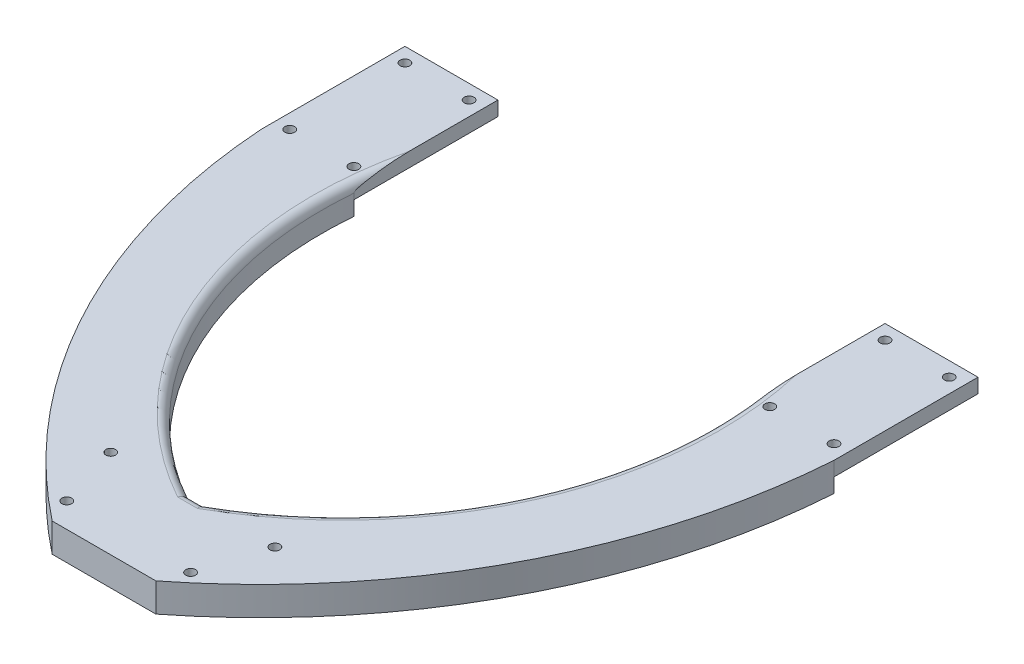
SolidWorks part; units mm, degrees
ref_plane "Ebene vorne" through (0, 0, 0) normal (0, 0, 1) x (1, 0, 0)
ref_plane "Ebene oben" through (0, 0, 0) normal (0, 1, 0) x (1, 0, 0)
ref_plane "Ebene rechts" through (0, 0, 0) normal (1, 0, 0) x (0, 0, -1)
sketch "Skizze1" plane through (0, 0, 0) normal (0, 1, 0) x (1, 0, 0)
  line L1 (-99.5, -210) -> (99.5, -210)
  line L2 (-99.5, -210) -> (-99.5, 210)
  line L3 (-99.5, 210) -> (99.5, 210)
  line L4 (99.5, -210) -> (99.5, 210)
  line L5 (-99.5, -210) -> (99.5, 210) construction
  line L6 (-99.5, 210) -> (99.5, -210) construction
  point P0 (0, 0)
  dimension "D1" = 199
  dimension "D2" = 420
extrude "Aufsatz-Linear austragen1" add sketch "Skizze1" along normal blind 10
ref_plane "Ebene1" through (0, -97.5366, 81.8429) normal (0, -0.766, 0.6428) x (1, 0, 0)
sketch "Skizze2" plane through (0, -97.5366, 81.8429) normal (0, -0.766, 0.6428) x (1, 0, 0)
  line L1 (-99.5, 167.2972) -> (99.5, 167.2972) construction
  circle A0 centre (0, 147.2972) radius 5
  dimension "D1" = 10
  dimension "D2" = 20
extrude "Schnitt-Linear austragen1" [suppressed] cut sketch "Skizze2" against normal blind 30 and the other way blind 10
sketch "Skizze3" [suppressed] plane through (0, -67.9923, 57.0523) normal (0, -0.766, 0.6428) x (1, 0, 0)
  circle A0 centre (0, 101.3345) radius 5
  dimension "D1" = 10
extrude "Aufsatz-Linear austragen2" [suppressed] add sketch "Skizze3" along normal blind 0.1
sketch "Skizze4" plane through (0, -97.5366, 81.8429) normal (0, -0.766, 0.6428) x (1, 0, 0)
  line L0 (0, 167.2972) -> (0, 159.9002) construction
  line L1 (-99.5, 167.2972) -> (99.5, 167.2972) construction
  line L2 (-25, 167.2972) -> (-25, 202.2972)
  line L3 (-25, 202.2972) -> (25, 202.2972)
  line L4 (-25, 167.2972) -> (25, 167.2972)
  line L5 (25, 167.2972) -> (25, 202.2972)
  point P10 (0, 202.2972)
  dimension "D1" = 50
  dimension "D2" = 35
extrude "Aufsatz-Linear austragen3" [suppressed] add sketch "Skizze4" against normal blind 10 separate body
sketch "Skizze5" plane through (0, 10, 0) normal (0, 1, 0) x (1, 0, 0)
  line L0 (0, 0) -> (0, -210) construction
  line L1 (-99.5, -210) -> (99.5, -210) construction
  line L2 (99.5, -210) -> (18, -210)
  line L3 (-18, -210) -> (-99.5, -56)
  line L4 (-99.5, 210) -> (-99.5, -210) construction
  line L5 (-99.5, -56) -> (-99.5, -210)
  line L6 (-99.5, -210) -> (-18, -210)
  line L7 (99.5, -56) -> (99.5, -210)
  line L8 (18, -210) -> (99.5, -56)
  line L9 (-99.5, 210) -> (-99.5, 125)
  line L10 (-99.5, 125) -> (99.5, 125)
  line L11 (99.5, -210) -> (99.5, 210) construction
  line L12 (99.5, 125) -> (99.5, 210)
  line L13 (99.5, 210) -> (-99.5, 210)
  line L14 (67.211, -56) -> (-67.211, -56)
  line L15 (-67.211, -56) -> (-2.6461, -178)
  line L16 (67.211, -56) -> (2.6461, -178)
  line L17 (-2.6461, -178) -> (2.6461, -178)
  line L18 (2.6461, -178) -> (0, -183) construction
  line L19 (-2.6461, -178) -> (0, -183) construction
  point P27 (0, -56)
  dimension "D1" = 36
  dimension "D2" = 154
  dimension "D3" = 85
  dimension "D4" = 32
  dimension "D5" = 27
extrude "Schnitt-Linear austragen2" cut sketch "Skizze5" against normal blind 10
sketch "Skizze6" plane through (0, 10, 0) normal (0, 1, 0) x (1, 0, 0)
  line L0 (0, -210) -> (0, -178) construction
  line L1 (-18, -210) -> (18, -210) construction
  line L2 (-2.6461, -178) -> (2.6461, -178) construction
  line L3 (0, -196.59) -> (-21.075, -196.59) construction
  circle A0 centre (-11, -205) radius 1.7
  circle A1 centre (-11, -188.18) radius 1.7
  circle A2 centre (11, -205) radius 1.7
  circle A3 centre (11, -188.18) radius 1.7
  dimension "D1" = 3.4
  dimension "D2" = 11
  dimension "D3" = 5
  dimension "D4" = 13.41
extrude "Schnitt-Linear austragen3" [suppressed] cut sketch "Skizze6" against normal through all
sketch "Skizze7" [suppressed] plane through (0, 0, 0) normal (0, -1, 0) x (1, 0, 0)
  line L0 (-11, 205) -> (-11, 210) construction
  line L1 (-18, 210) -> (18, 210) construction
  line L2 (-11, 205) -> (-5.1092, 205) construction
  line L3 (-11, 208.4064) -> (-8.05, 206.7032)
  line L4 (-8.05, 206.7032) -> (-8.05, 203.2968)
  line L5 (-11, 201.5936) -> (-8.05, 203.2968)
  line L6 (-11, 201.5936) -> (-13.95, 203.2968)
  line L7 (-13.95, 206.7032) -> (-13.95, 203.2968)
  line L8 (-11, 208.4064) -> (-13.95, 206.7032)
  line L9 (0, 210) -> (0, 121.6034) construction
  line L10 (11, 205) -> (11, 188.18) construction
  line L11 (11, 196.59) -> (0, 196.59) construction
  line L12 (11, 208.4064) -> (8.05, 206.7032)
  line L13 (11, 201.5936) -> (8.05, 203.2968)
  line L14 (8.05, 206.7032) -> (8.05, 203.2968)
  line L15 (11, 201.5936) -> (13.95, 203.2968)
  line L16 (13.95, 206.7032) -> (13.95, 203.2968)
  line L17 (11, 208.4064) -> (13.95, 206.7032)
  line L18 (-8.05, 186.4768) -> (-8.05, 189.8832)
  line L19 (-11, 191.5864) -> (-13.95, 189.8832)
  line L20 (-11, 191.5864) -> (-8.05, 189.8832)
  line L21 (-13.95, 186.4768) -> (-13.95, 189.8832)
  line L22 (-11, 184.7736) -> (-13.95, 186.4768)
  line L23 (-11, 184.7736) -> (-8.05, 186.4768)
  line L24 (8.05, 186.4768) -> (8.05, 189.8832)
  line L25 (11, 191.5864) -> (8.05, 189.8832)
  line L26 (11, 191.5864) -> (13.95, 189.8832)
  line L27 (13.95, 186.4768) -> (13.95, 189.8832)
  line L28 (11, 184.7736) -> (13.95, 186.4768)
  line L29 (11, 184.7736) -> (8.05, 186.4768)
  point P10 (-8.05, 205)
  dimension "D1" = 120
  dimension "D2" = 5.9
extrude "Schnitt-Linear austragen4" [suppressed] cut sketch "Skizze7" against normal blind 4
sketch "Skizze8" plane through (0, 10, 0) normal (0, 1, 0) x (1, 0, 0)
  line L0 (99.5, 115.41) -> (78.872, 115.41) construction
  line L1 (99.5, -56) -> (99.5, 125) construction
  line L2 (-99.5, 125) -> (99.5, 125) construction
  dimension "D1" = 9.59
ref_plane "Ebene2" through (0, 62.6966, -52.6087) normal (0, 0.766, -0.6428) x (-1, 0, 0)
sketch "Skizze9" plane through (0, 62.6966, -52.6087) normal (0, 0.766, -0.6428) x (-1, 0, 0)
  line L0 (-99.5, -81.9813) -> (-78.872, -81.9813) construction
  line L1 (-99.5, 49.3264) -> (-99.5, -89.3277) construction
  line L2 (0, -45.2589) -> (0, -16.2619) construction
  circle A0 centre (-94.5, -81.9813) radius 1.7
  circle A1 centre (94.5, -81.9813) radius 1.7
  circle A2 centre (-30, -81.9813) radius 1.7
  circle A3 centre (30, -81.9813) radius 1.7
  dimension "D1" = 3.4
  dimension "D2" = 5
  dimension "D3" = 30
extrude "Schnitt-Linear austragen5" [suppressed] cut sketch "Skizze9" against normal through all and the other way through all
ref_plane "Ebene3" through (0, 55.0361, -46.1808) normal (0, 0.766, -0.6428) x (-1, 0, 0)
sketch "Skizze10" [suppressed] plane through (0, 55.0361, -46.1808) normal (0, 0.766, -0.6428) x (-1, 0, 0)
  line L0 (-95, -81.9813) -> (-100, -81.9813) construction
  line L1 (-95, -81.9813) -> (-95, -30.0694) construction
  line L2 (-95, -78.7482) -> (-97.8, -80.3647)
  line L3 (-97.8, -80.3647) -> (-97.8, -83.5979)
  line L4 (-95, -85.2145) -> (-97.8, -83.5979)
  line L5 (-95, -85.2145) -> (-92.2, -83.5979)
  line L6 (-92.2, -80.3647) -> (-92.2, -83.5979)
  line L7 (-95, -78.7482) -> (-92.2, -80.3647)
  line L8 (0, 0) -> (0, -45.6283) construction
  line L9 (-30, -81.9813) -> (-95, -81.9813) construction
  line L10 (-62.5, -81.9813) -> (-62.5, -23.1343) construction
  line L11 (-32.8, -80.3647) -> (-32.8, -83.5979)
  line L12 (-30, -85.2145) -> (-32.8, -83.5979)
  line L13 (-30, -85.2145) -> (-27.2, -83.5979)
  line L14 (-27.2, -80.3647) -> (-27.2, -83.5979)
  line L15 (-30, -78.7482) -> (-27.2, -80.3647)
  line L16 (-30, -78.7482) -> (-32.8, -80.3647)
  line L17 (95, -78.7482) -> (92.2, -80.3647)
  line L18 (92.2, -80.3647) -> (92.2, -83.5979)
  line L19 (95, -85.2145) -> (92.2, -83.5979)
  line L20 (95, -85.2145) -> (97.8, -83.5979)
  line L21 (97.8, -80.3647) -> (97.8, -83.5979)
  line L22 (95, -78.7482) -> (97.8, -80.3647)
  line L23 (30, -78.7482) -> (32.8, -80.3647)
  line L24 (30, -78.7482) -> (27.2, -80.3647)
  line L25 (27.2, -80.3647) -> (27.2, -83.5979)
  line L26 (30, -85.2145) -> (27.2, -83.5979)
  line L27 (30, -85.2145) -> (32.8, -83.5979)
  line L28 (32.8, -80.3647) -> (32.8, -83.5979)
  point P9 (-97.8, -81.9813)
  point P31 (97.8, -81.9813)
  dimension "D1" = 120
  dimension "D2" = 5.6
extrude "Schnitt-Linear austragen6" [suppressed] cut sketch "Skizze10" against normal blind 10 and the other way blind 5
sketch "Skizze13" plane through (0, 10, 0) normal (0, 1, 0) x (1, 0, 0)
  line L0 (67.211, -56) -> (99.5, -56) construction
  line L1 (67.211, -56) -> (92.4353, -69.3492) construction
  line L2 (99.5, -56) -> (18, -210) construction
  line L3 (0, 0) -> (0, -38.1435) construction
  line L4 (2.6461, -178) -> (67.211, -56) construction
  line L5 (79.8232, -62.6746) -> (103.8351, -17.3024) construction
  line L6 (99.5, -56) -> (99.5, 125) construction
  line L7 (83.3555, -56) -> (83.3555, -1) construction
  line L8 (93.5, -58.8065) -> (101.0692, -44.504) construction
  line L9 (83.1285, -86.935) -> (57.9043, -73.5858) construction
  line L10 (71.7911, -80.935) -> (86.3039, -80.935) construction
  circle A0 centre (93.5, -58.8065) radius 1.7
  circle A1 centre (72.5142, -58.8065) radius 1.7
  circle A2 centre (81.7891, -80.935) radius 1.7
  circle A3 centre (-81.7891, -80.935) radius 1.7
  circle A4 centre (-93.5, -58.8065) radius 1.7
  circle A5 centre (-72.5142, -58.8065) radius 1.7
  dimension "D1" = 6
  dimension "D5" = 35
  dimension "D3" = 3.4
  dimension "D6" = 3.4
  dimension "D2" = 6
  dimension "D4" = 6
extrude "Schnitt-Linear austragen7" [suppressed] cut sketch "Skizze13" against normal through all
sketch "Skizze14" plane through (100.8819, 0, 53.3888) normal (0.8839, 0, 0.4678) x (0.4678, 0, -0.8839)
  line L0 (-37.9543, 5) -> (-37.9543, 10)
  line L5 (-2.9543, 0) -> (-2.9543, 10) construction
  line L6 (-37.9543, 5) -> (-2.9543, 5)
  line L7 (-2.9543, 10) -> (-177.1905, 10) construction
  line L8 (-37.9543, 10) -> (-2.9543, 10)
  line L9 (-2.9543, 10) -> (-2.9543, 5)
  dimension "D1" = 35
extrude "Schnitt-Linear austragen8" [suppressed] cut sketch "Skizze14" against normal up to surface (28.9525 mm away) up to face at (34.9286, 5, 117)
mirror "Spiegeln1" [suppressed] about plane through (0, 0, 0) normal (1, 0, 0)
sketch "Skizze15" [suppressed] plane through (95, 0, 0) normal (1, 0, 0) x (0, 0, -1)
  line L0 (4, 10) -> (4, 0)
  line L1 (4, 0) -> (65, 0)
  line L2 (65, 0) -> (65, 10)
  line L3 (65, 10) -> (4, 10)
extrude "Schnitt-Linear austragen9" [suppressed] cut sketch "Skizze15" against normal through all
sketch "Skizze16" [suppressed] plane through (0, 0, 0) normal (0, -1, 0) x (1, 0, 0)
  line L0 (0, 210) -> (0, 178) construction
  line L1 (-18, 210) -> (18, 210) construction
  line L2 (-2.8247, 178) -> (2.8247, 178) construction
  line L3 (11, 196.59) -> (0, 196.59) construction
  line L4 (11, 205) -> (11, 188.18) construction
  line L6 (-17.5, 193.09) -> (17.5, 193.09)
  line L7 (-17.5, 193.09) -> (-17.5, 200.09)
  line L8 (-17.5, 200.09) -> (17.5, 200.09)
  line L9 (17.5, 193.09) -> (17.5, 200.09)
  line L10 (-17.5, 193.09) -> (17.5, 200.09) construction
  line L11 (-17.5, 200.09) -> (17.5, 193.09) construction
  dimension "D1" = 7
  dimension "D2" = 35
extrude "Schnitt-Linear austragen10" [suppressed] cut sketch "Skizze16" against normal blind 5
sketch "Skizze17" [suppressed] plane through (17.5, 0, 0) normal (-1, 0, 0) x (0, 0, 1)
  line L0 (196.59, 0) -> (196.59, 11.1261) construction
  line L1 (193.09, 0) -> (200.09, 0) construction
  line L2 (193.09, 5) -> (196.59, 8.5)
  line L3 (196.59, 8.5) -> (200.09, 5)
  line L4 (200.09, 5) -> (193.09, 5)
  dimension "D1" = 90
extrude "Schnitt-Linear austragen11" [suppressed] cut sketch "Skizze17" along normal up to surface (35 mm away)
sketch "Skizze18" [suppressed] plane through (0, 10, 0) normal (0, 1, 0) x (1, 0, 0)
  line L0 (0, -210) -> (0, 0) construction
  line L1 (-18, -210) -> (18, -210) construction
  line L2 (62.5765, -72.2325) -> (35.4483, -67.5372)
  line L3 (15.3378, -155.8503) -> (-22.1774, -134.6566)
  line L4 (2.8247, -178) -> (62.5765, -72.2325) construction
  line L5 (-15.3378, -155.8503) -> (22.1774, -134.6566)
  line L6 (58.6594, -79.166) -> (40.7308, -76.063)
  line L7 (0, -147.1854) -> (19.5429, -147.1854) construction
  line L8 (0, -95.4) -> (31.4297, -95.4) construction
  line L9 (11.6488, -162.3803) -> (0, -155.7995)
  line L10 (-71.7468, -56) -> (-2.8247, -178) construction
  line L11 (0, -95.4) -> (-37.5153, -116.5937) construction
  line L12 (-37.5153, -116.5937) -> (-39.2566, -117.5774) construction
  line L13 (-11.6488, -162.3803) -> (0, -155.7995)
  line L14 (-58.6594, -79.166) -> (-40.7308, -76.063)
  line L15 (-62.5765, -72.2325) -> (-35.4483, -67.5372)
  circle A0 centre (0, -95.4) radius 33.5
  arc A1 (7.4594, -151.3994) -> (7.4594, -142.9713) centre (9.84, -147.1854) cw
  arc A2 (-7.4594, -151.3994) -> (-7.4594, -142.9713) centre (-9.84, -147.1854) ccw
  circle A3 centre (0, -95.4) radius 45.0879
  point P17 (0, -147.1854)
  point P36 (5, -147.1854)
  point P40 (-5, -147.1854)
  line M16 (62.5765, -72.2325) -> (2.8247, -178)
  line M18 (-2.8247, -178) -> (-71.7468, -56)
  dimension "D2" = 67
  dimension "D5" = 2
  dimension "D4" = 10
  dimension "D1" = 114.6
  dimension "D3" = 7.5
  dimension "D6" = 7.5
extrude "Aufsatz-Linear austragen4" [suppressed] add sketch "Skizze18" against normal blind 10 contours A3 L15 L14 M18 | A3 A0 M16 M18 | A3 L6 L2 M16 | A2 L5 L3 | A3 L3 L5 | L3 A1 L5 | L13 L9 L3 L5 M18 M16
sketch "Skizze19" [suppressed] plane through (0, 0, 0) normal (0, -1, 0) x (1, 0, 0)
  circle A0 centre (0, 35.4) radius 31.5
  circle A1 centre (0, 35.4) radius 33.5
  circle A2 centre (0, 35.4) radius 33.5 construction
  dimension "D1" = 63
extrude "Aufsatz-Linear austragen5" [suppressed] add sketch "Skizze19" against normal blind 1
sketch "Skizze20" plane through (0, 10, 0) normal (0, 1, 0) x (1, 0, 0)
  line L0 (99.5, 119.52) -> (55.4083, 119.52) construction
  line L1 (99.5, -56) -> (99.5, 125) construction
  line L2 (-99.5, 125) -> (99.5, 125) construction
  line L3 (0, 125) -> (0, 96.9732) construction
  line L4 (105, 43.82) -> (35.5869, 43.82) construction
  circle A0 centre (90.5, 119.52) radius 1.7
  circle A1 centre (48.5, 119.52) radius 1.7
  circle A2 centre (-48.5, 119.52) radius 1.7
  circle A3 centre (-90.5, 119.52) radius 1.7
  circle A4 centre (87, 43.82) radius 1.7
  circle A5 centre (52, 43.82) radius 1.7
  circle A6 centre (-87, 43.82) radius 1.7
  circle A7 centre (-52, 43.82) radius 1.7
  dimension "D1" = 3.4
  dimension "D2" = 5.48
  dimension "D3" = 9
  dimension "D4" = 42
  dimension "D5" = 75.7
  dimension "D6" = 12.5
  dimension "D7" = 35
extrude "Schnitt-Linear austragen12" cut sketch "Skizze20" against normal through all
sketch "Skizze21" plane through (0, 10, 0) normal (0, 1, 0) x (1, 0, 0)
  line L0 (-67.211, -56) -> (-67.211, 19)
  line L1 (-67.211, 19) -> (67.211, 19)
  line L2 (67.211, 19) -> (67.211, -56)
  line L3 (67.211, -56) -> (-67.211, -56) construction
  line L4 (-67.211, -56) -> (67.211, -56)
  dimension "D1" = 75
extrude "Schnitt-Linear austragen13" cut sketch "Skizze21" against normal through all
sketch "Skizze22" plane through (0, 10, 0) normal (0, 1, 0) x (1, 0, 0)
  line L0 (-67.211, -56) -> (-2.6461, -178)
  arc A0 (-67.211, -56) -> (-2.6461, -178) centre (60.0769, -66.7211) ccw
  line M19 (-2.6461, -178) -> (-67.211, -56)
extrude "Schnitt-Linear austragen14" cut sketch "Skizze22" against normal through all contours M19 region at (-42.1385, 10, 120.8156)
sketch "Skizze23" plane through (0, 10, 0) normal (0, 1, 0) x (1, 0, 0)
  line L0 (-18, -210) -> (-99.5, -56) construction
  line L1 (-99.5, -56) -> (-18, -210)
  arc A0 (-18, -210) -> (-99.5, -56) centre (114.4449, -41.3416) cw
  arc A2 (-67.211, -56) -> (-2.6461, -178) centre (60.0769, -66.7211) ccw construction
  dimension "D1" = 60
extrude "Aufsatz-Linear austragen6" add sketch "Skizze23" against normal blind 10
mirror "Spiegeln2" about plane through (0, 0, 0) normal (1, 0, 0) of "Aufsatz-Linear austragen6", "Schnitt-Linear austragen14"
sketch "Skizze25" plane through (0, 10, 0) normal (0, 1, 0) x (1, 0, 0)
  line L0 (-99.5, -56) -> (-67.211, -56) construction
  line L1 (-99.5, -6) -> (-99.5, -56) construction
  line L2 (-99.5, -6) -> (-67.211, -6) construction
  line L3 (-67.211, 19) -> (-67.211, -56) construction
  line L4 (-83.3555, -6) -> (-83.3555, -56) construction
  line L5 (-99.5, -31) -> (-67.211, -31) construction
  line L6 (-99.5, 125) -> (-99.5, -56) construction
  circle A0 centre (-94.5, -11) radius 1.7
  circle A1 centre (-72.211, -11) radius 1.7
  circle A2 centre (-72.211, -51) radius 1.7
  circle A3 centre (-94.5, -51) radius 1.7
  dimension "D2" = 3.4
  dimension "D1" = 50
  dimension "D3" = 5
  dimension "D4" = 5
extrude "Schnitt-Linear austragen15" cut sketch "Skizze25" against normal through all
sketch "Skizze26" plane through (-99.5, 0, 0) normal (-1, 0, 0) x (0, 0, 1)
  line L0 (56, 5) -> (56, 0)
  line L1 (56, 0) -> (56, 10) construction
  line L2 (56, 5) -> (6, 5)
  line L3 (6, 5) -> (6, 10)
  line L4 (-125, 0) -> (56, 0) construction
  line L5 (5.0128, 19.5087) -> (6, 10)
  line L6 (5.0128, 19.5087) -> (-137.7077, 19.5087)
  line L7 (-137.7077, 19.5087) -> (-137.7077, -14.4017)
  line L8 (-137.7077, -14.4017) -> (4.1968, -14.4017)
  line L9 (4.1968, -14.4017) -> (56, 0)
  line L10 (-125, 10) -> (56, 10) construction
mirror "Spiegeln3" about plane through (0, 0, 0) normal (1, 0, 0) of "Schnitt-Linear austragen15"
extrude "Schnitt-Linear austragen16" cut sketch "Skizze26" against normal through all
fillet "Verrundung1" radius 3 3 edges at (52.8259, 10, 126.4716) (-52.8259, 10, 126.4716) (0, 10, 178)
sketch "Skizze27" plane through (0, 10, 0) normal (0, 1, 0) x (1, 0, 0)
  line L0 (0, -210) -> (0, -164.5001) construction
  line L1 (-18, -210) -> (18, -210) construction
  line L2 (17.5, -210) -> (17.5, -183.18) construction
  line L3 (-17.5, -210) -> (-17.5, -183.18) construction
  line L4 (17.5, -210) -> (32.5, -197.4135) construction
  line L5 (-17.5, -183.18) -> (17.5, -183.18) construction
  line L6 (17.5, -183.18) -> (32.5, -170.5935) construction
  line L7 (32.5, -170.5935) -> (32.5, -197.4135) construction
  line L8 (-17.5, -210) -> (-32.5, -197.4135) construction
  line L9 (-32.5, -170.5935) -> (-32.5, -197.4135) construction
  line L10 (-17.5, -183.18) -> (-32.5, -170.5935) construction
  line L11 (28.5, -179.1715) -> (32.5, -179.1715) construction
  line L12 (28.5, -179.1715) -> (25.9288, -176.1074) construction
  line L13 (21.5, -201.422) -> (24.0712, -204.4862) construction
  line L14 (21.5, -201.422) -> (17.5, -201.422) construction
  circle A0 centre (28.5, -179.1715) radius 1.7
  circle A1 centre (21.5, -201.422) radius 1.7
  circle A2 centre (-21.5, -201.422) radius 1.7
  circle A3 centre (-28.5, -179.1715) radius 1.7
  dimension "D5" = 3.4
  dimension "D1" = 17.5
  dimension "D2" = 140
  dimension "D3" = 26.82
  dimension "D4" = 15
  dimension "D6" = 4
  dimension "D7" = 4
extrude "Schnitt-Linear austragen17" cut sketch "Skizze27" against normal through all
sketch "Skizze28" plane through (0, 0, 0) normal (0, -1, 0) x (1, 0, 0)
  line L0 (21.5, 201.422) -> (21.5, 205.9223) construction
  line L1 (21.5, 201.422) -> (27.5804, 201.422) construction
  line L2 (21.5, 204.8283) -> (24.45, 203.1252)
  line L3 (24.45, 203.1252) -> (24.45, 199.7188)
  line L4 (21.5, 198.0156) -> (24.45, 199.7188)
  line L5 (21.5, 198.0156) -> (18.55, 199.7188)
  line L6 (18.55, 203.1252) -> (18.55, 199.7188)
  line L7 (21.5, 204.8283) -> (18.55, 203.1252)
  line L8 (28.5, 179.1715) -> (28.5, 188.5672) construction
  line L9 (28.5, 179.1715) -> (36.4607, 179.1715) construction
  line L10 (28.5, 182.5779) -> (31.45, 180.8747)
  line L11 (31.45, 180.8747) -> (31.45, 177.4683)
  line L12 (28.5, 175.7652) -> (31.45, 177.4683)
  line L13 (28.5, 175.7652) -> (25.55, 177.4683)
  line L14 (25.55, 180.8747) -> (25.55, 177.4683)
  line L15 (28.5, 182.5779) -> (25.55, 180.8747)
  line L16 (0, 210) -> (0, 191.8778) construction
  line L17 (-18, 210) -> (18, 210) construction
  line L18 (-28.5, 182.5779) -> (-25.55, 180.8747)
  line L19 (-25.55, 180.8747) -> (-25.55, 177.4683)
  line L20 (-28.5, 175.7652) -> (-25.55, 177.4683)
  line L21 (-28.5, 175.7652) -> (-31.45, 177.4683)
  line L22 (-31.45, 180.8747) -> (-31.45, 177.4683)
  line L23 (-28.5, 182.5779) -> (-31.45, 180.8747)
  line L24 (-21.5, 201.422) -> (-21.5, 205.9223) construction
  line L25 (-21.5, 204.8283) -> (-18.55, 203.1252)
  line L26 (-18.55, 203.1252) -> (-18.55, 199.7188)
  line L27 (-21.5, 198.0156) -> (-18.55, 199.7188)
  line L28 (-21.5, 198.0156) -> (-24.45, 199.7188)
  line L29 (-24.45, 203.1252) -> (-24.45, 199.7188)
  line L30 (-21.5, 204.8283) -> (-24.45, 203.1252)
  point P9 (24.45, 201.422)
  point P12 (18.55, 201.422)
  point P22 (31.45, 179.1715)
  point P35 (-31.45, 179.1715)
  point P44 (-18.55, 201.422)
  point P45 (-24.45, 201.422)
  dimension "D1" = 120
  dimension "D2" = 5.9
  dimension "D3" = 5.9
  dimension "D4" = 120
extrude "Schnitt-Linear austragen18" cut sketch "Skizze28" against normal blind 5
